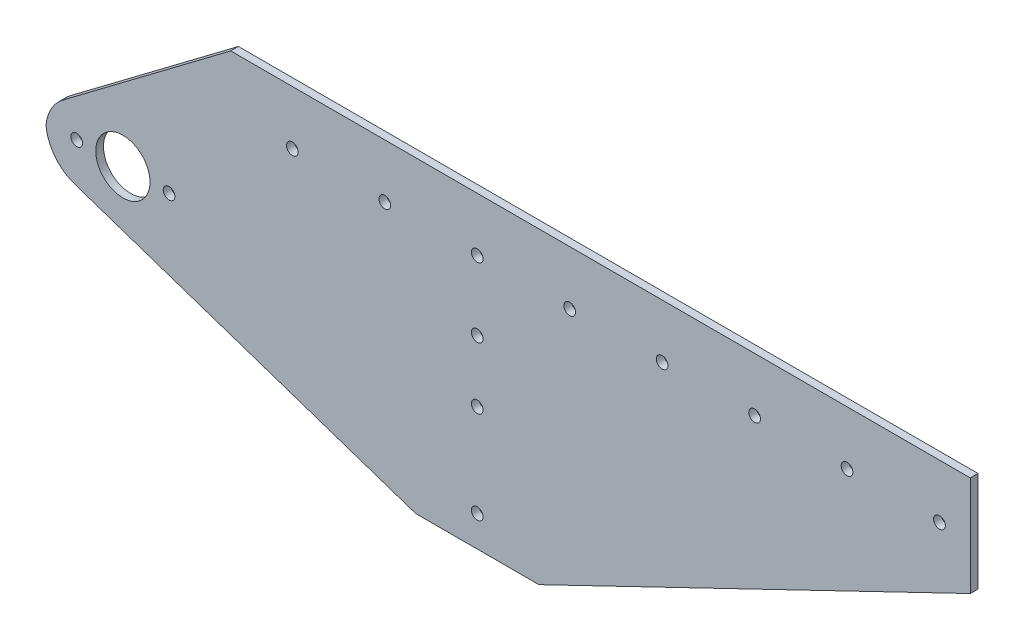
SolidWorks part; units mm, degrees
ref_plane "Front Plane" through (0, 0, 0) normal (0, 0, 1) x (1, 0, 0)
ref_plane "Top Plane" through (0, 0, 0) normal (0, 1, 0) x (1, 0, 0)
ref_plane "Right Plane" through (0, 0, 0) normal (1, 0, 0) x (0, 0, -1)
sketch "Sketch1" plane through (0, 0, 0) normal (0, 0, 1) x (1, 0, 0)
  line L0 (-304.8, 0) -> (0, 0)
  line L1 (0, 0) -> (0, -41.275)
  line L2 (0, -41.275) -> (-177.8, -127)
  line L3 (-177.8, -127) -> (-228.6, -127)
  line L4 (-228.6, -127) -> (-381, -75.7257)
  line L5 (-381, -75.7257) -> (-381, 0)
  line L6 (-381, 0) -> (-304.8, 0)
  point P7 (-160.1716, -31.2327)
  point P9 (-159.4551, -43.7124)
  point P10 (-41.1314, -120.4312)
  point P11 (193.1153, -25.4)
  point P12 (183.559, -25.4)
  point P13 (0, 0)
  point P14 (-355.6, -75.7257)
  dimension "D1" = 50.8
  dimension "D2" = 304.8
  dimension "D3" = 41.275
  dimension "D4" = 76.2
  dimension "D5" = 127
  dimension "D6" = 76.2
extrude "Boss-Extrude1" add sketch "Sketch1" along normal blind 3.175
sketch "Sketch2" plane through (0, 0, 3.175) normal (0, 0, 1) x (1, 0, 0)
  line L0 (-381, 0) -> (-381, -75.7257) construction
  line L1 (0, 0) -> (-381, 0) construction
  line L2 (-228.6, -127) -> (-177.8, -127) construction
  line L3 (0, -41.275) -> (0, 0) construction
  circle A0 centre (-349.25, -63.5) radius 11.176
  circle A1 centre (-203.2, -114.3) radius 2.413
  circle A2 centre (-203.2, -50.8) radius 2.413
  circle A3 centre (-203.2, -76.2) radius 2.413
  circle A4 centre (-203.2, -22.225) radius 2.413
  circle A5 centre (-12.7, -22.225) radius 2.413
  circle A6 centre (-50.8, -22.225) radius 2.413
  circle A7 centre (-88.9, -22.225) radius 2.413
  circle A8 centre (-127, -22.225) radius 2.413
  circle A9 centre (-165.1, -22.225) radius 2.413
  circle A10 centre (-203.2, -22.225) radius 2.413
  circle A11 centre (-241.3, -22.225) radius 2.413
  circle A12 centre (-279.4, -22.225) radius 2.413
  circle A13 centre (-317.5, -22.225) radius 2.413
  dimension "D1" = 22.352
  dimension "D4" = 4.826
  dimension "D5" = 4.826
  dimension "D6" = 4.826
  dimension "D10" = 4.826
  dimension "D15" = 4.826
  dimension "D2" = 31.75
  dimension "D3" = 63.5
  dimension "D7" = 12.7
  dimension "D8" = 38.1
  dimension "D9" = 25.4
  dimension "D11" = 22.225
  dimension "D12" = 25.4
  dimension "D13" = 12.7
  dimension "D14" = 19.05
  dimension "D16" = 9
extrude "Cut-Extrude1" cut sketch "Sketch2" against normal blind 3.175 contours A0 | A12 | A11 | A4 | A2 | A9 | A8 | A7 | A5 | A3 | A1 | A6 region at (-349.25, -63.5, 3.175) region at (-203.2, -114.3, 3.175) region at (-203.2, -50.8, 3.175) region at (-203.2, -76.2, 3.175) region at (-203.2, -22.225, 3.175) region at (-12.7, -22.225, 3.175) region at (-50.8, -22.225, 3.175) region at (-88.9, -22.225, 3.175) region at (-127, -22.225, 3.175) region at (-165.1, -22.225, 3.175) region at (-241.3, -22.225, 3.175) region at (-279.4, -22.225, 3.175)
chamfer "Chamfer2" distance 76.2 angle 37 1 edges at (-381, 0, 1.5875) first distance on face at (-190.5, 0, 1.5875)
fillet "Fillet2" radius 17.62 2 edges at (-381, -75.7257, 1.5875) (-381, -57.4208, 1.5875)
sketch "Sketch3" plane through (0, 0, 3.175) normal (0, 0, 1) x (1, 0, 0)
  line L0 (-360.426, -63.5) -> (-338.074, -63.5) construction
  circle A0 centre (-368.3, -63.5) radius 2.413
  circle A1 centre (-330.2, -63.5) radius 2.413
  circle A2 centre (-349.25, -63.5) radius 11.176 construction
  dimension "D3" = 4.826
  dimension "D4" = 4.826
  dimension "D1" = 19.05
  dimension "D2" = 19.05
extrude "Cut-Extrude2" cut sketch "Sketch3" against normal blind 3.175
